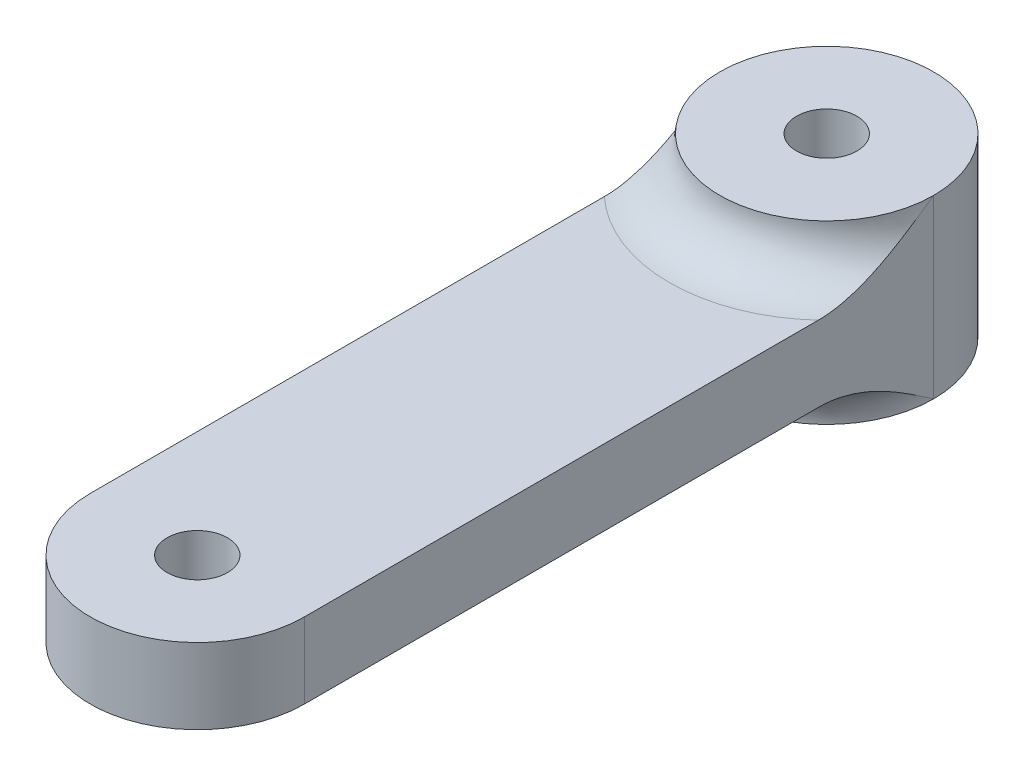
SolidWorks part; units mm, degrees
ref_plane "Front Plane" through (0, 0, 0) normal (0, 0, 1) x (1, 0, 0)
ref_plane "Top Plane" through (0, 0, 0) normal (0, 1, 0) x (1, 0, 0)
ref_plane "Right Plane" through (0, 0, 0) normal (1, 0, 0) x (0, 0, -1)
sketch "Sketch1" plane through (0, 0, 0) normal (0, 1, 0) x (1, 0, 0)
  line L0 (0, 0) -> (0, -25) construction
  line L1 (4.25, 0) -> (4.25, -25)
  line L2 (-4.25, 0) -> (-4.25, -25)
  arc A0 (4.25, 0) -> (-4.25, 0) centre (0, 0) ccw
  arc A1 (-4.25, -25) -> (4.25, -25) centre (0, -25) ccw
  circle A2 centre (0, 0) radius 1.2
  circle A3 centre (0, -25) radius 1.2
  point P3 (0, -12.5)
  dimension "D3" = 2.4
  dimension "D4" = 2.4
  dimension "D1" = 8.5
  dimension "D2" = 25
extrude "Boss-Extrude1" add sketch "Sketch1" along normal blind 7
sketch "Sketch2" plane through (0, 7, 0) normal (0, 1, 0) x (1, 0, 0)
  line L0 (-4.25, 0) -> (-4.25, -29.25)
  line L1 (-4.25, -29.25) -> (4.25, -29.25)
  line L2 (4.25, -29.25) -> (4.25, 0)
  arc A0 (-4.25, 0) -> (4.25, 0) centre (0, 0) ccw
  arc A1 (4.25, 0) -> (-4.25, 0) centre (0, 0) ccw construction
  arc A2 (-4.25, -25) -> (4.25, -25) centre (0, -25) ccw construction
extrude "Cut-Extrude1" cut sketch "Sketch2" against normal blind 2
sketch "Sketch3" plane through (0, 0, 0) normal (0, -1, 0) x (1, 0, 0)
  line L0 (4.25, 25) -> (4.25, 0) construction
  line L1 (-4.25, 0) -> (-4.25, 29.25)
  line L2 (-4.25, 29.25) -> (4.25, 29.25)
  line L3 (4.25, 29.25) -> (4.25, 0)
  arc A0 (-4.25, 0) -> (4.25, 0) centre (0, 0) cw
  arc A1 (4.25, 25) -> (-4.25, 25) centre (0, 25) ccw construction
extrude "Cut-Extrude2" cut sketch "Sketch3" against normal blind 2
fillet "Fillet1" radius 2 2 edges at (0, 5, 4.25) (0, 2, 4.25)
